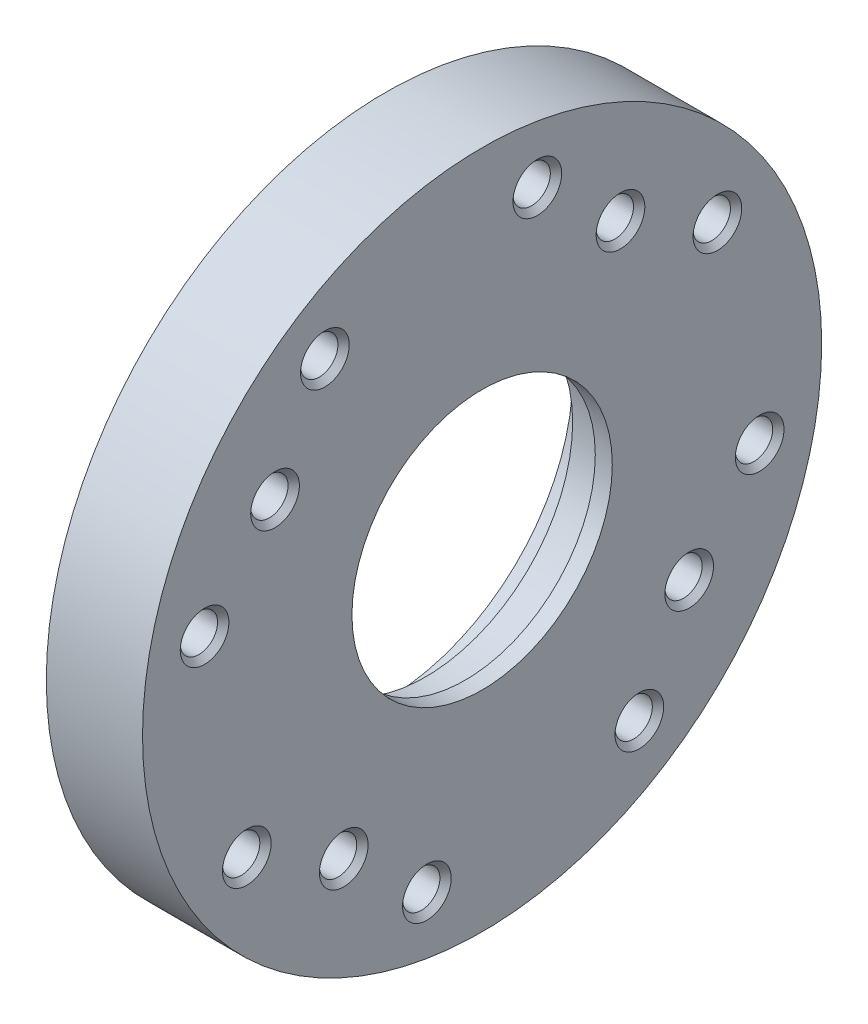
SolidWorks part; units mm, degrees
ref_plane "Front Plane" through (0, 0, 0) normal (0, 0, 1) x (1, 0, 0)
ref_plane "Top Plane" through (0, 0, 0) normal (0, 1, 0) x (1, 0, 0)
ref_plane "Right Plane" through (0, 0, 0) normal (1, 0, 0) x (0, 0, -1)
sketch "Sketch1" plane through (0, 0, 0) normal (0, 0, 1) x (1, 0, 0)
  line L0 (0, 0) -> (14, 0) construction
  line L1 (0, 60) -> (0, 33)
  line L2 (0, 33) -> (7, 33)
  line L3 (7, 33) -> (7, 26)
  line L4 (7, 26) -> (14, 26)
  line L5 (14, 26) -> (14, 23)
  line L6 (14, 23) -> (17, 23)
  line L7 (17, 23) -> (17, 60)
  line L8 (17, 60) -> (0, 60)
  dimension "D1" = 17
  dimension "D2" = 26
  dimension "D3" = 7
  dimension "D4" = 3
  dimension "D5" = 60
  dimension "D6" = 33
  dimension "D7" = 3
revolve "Revolve1" add sketch "Sketch1" angle 360 about L0
sketch "Sketch2" plane through (0, 0, 0) normal (-1, 0, 0) x (0, 0, 1)
  circle A0 centre (0, 0) radius 40 construction
  circle A1 centre (0, 40) radius 2.5
  circle A2 centre (15.3073, 36.9552) radius 2.5
  circle A3 centre (28.2843, 28.2843) radius 2.5
  circle A4 centre (36.9552, 15.3073) radius 2.5
  circle A5 centre (40, 0) radius 2.5
  circle A6 centre (36.9552, -15.3073) radius 2.5
  circle A7 centre (28.2843, -28.2843) radius 2.5
  circle A8 centre (15.3073, -36.9552) radius 2.5
  circle A9 centre (0, -40) radius 2.5
  circle A10 centre (-15.3073, -36.9552) radius 2.5
  circle A11 centre (-28.2843, -28.2843) radius 2.5
  circle A12 centre (-36.9552, -15.3073) radius 2.5
  circle A13 centre (-40, 0) radius 2.5
  circle A14 centre (-36.9552, 15.3073) radius 2.5
  circle A15 centre (-28.2843, 28.2843) radius 2.5
  circle A16 centre (-15.3073, 36.9552) radius 2.5
  point P37 (0, 0)
  dimension "D1" = 80
  dimension "D2" = 5
  dimension "D3" = 16
extrude "Cut-Extrude1" cut sketch "Sketch2" against normal blind 4
sketch "Sketch3" plane through (17, 0, 0) normal (1, 0, 0) x (0, 0, -1)
  circle A0 centre (49.0393, -9.7545) radius 3
  circle A1 centre (27.7785, -41.5735) radius 3
  circle A2 centre (-9.7545, -49.0393) radius 3
  circle A3 centre (-41.5735, -27.7785) radius 3
  circle A4 centre (-49.0393, 9.7545) radius 3
  circle A5 centre (-27.7785, 41.5735) radius 3
  circle A6 centre (9.7545, 49.0393) radius 3
  circle A7 centre (41.5735, 27.7785) radius 3
  point P20 (0, 0)
  dimension "D2" = 6
  dimension "D1" = 8
extrude "Cut-Extrude4" cut sketch "Sketch3" against normal through all
sketch "Sketch4" [suppressed] plane through (17, 0, 0) normal (1, 0, 0) x (0, 0, -1)
  circle A0 centre (9.7545, 49.0393) radius 5.25
  circle A1 centre (41.5735, 27.7785) radius 5.25
  circle A2 centre (49.0393, -9.7545) radius 5.25
  circle A3 centre (27.7785, -41.5735) radius 5.25
  circle A4 centre (-9.7545, -49.0393) radius 5.25
  circle A5 centre (-41.5735, -27.7785) radius 5.25
  circle A6 centre (-49.0393, 9.7545) radius 5.25
  circle A7 centre (-27.7785, 41.5735) radius 5.25
  point P20 (0, 0)
  dimension "D1" = 10.5
  dimension "D2" = 8
extrude "Cut-Extrude5" [suppressed] cut sketch "Sketch4" against normal blind 4
sketch "Sketch5" plane through (17, 0, 0) normal (1, 0, 0) x (0, 0, -1)
  line L0 (9.7545, 49.0393) -> (0, 0) construction
  line L1 (0, 0) -> (24.4451, 36.5847) construction
  circle A0 centre (9.7545, 49.0393) radius 3.3
  circle A1 centre (41.5735, 27.7785) radius 3.3
  circle A2 centre (49.0393, -9.7545) radius 3.3
  circle A3 centre (27.7785, -41.5735) radius 3.3
  circle A4 centre (-9.7545, -49.0393) radius 3.3
  circle A5 centre (-41.5735, -27.7785) radius 3.3
  circle A6 centre (-49.0393, 9.7545) radius 3.3
  circle A7 centre (-27.7785, 41.5735) radius 3.3
  circle A8 centre (0, 0) radius 44 construction
  circle A9 centre (24.4451, 36.5847) radius 3.3
  circle A10 centre (36.5847, -24.4451) radius 3.3
  circle A11 centre (-24.4451, -36.5847) radius 3.3
  circle A12 centre (-36.5847, 24.4451) radius 3.3
  point P19 (0, 0)
  point P33 (0, 0)
  dimension "D1" = 6.6
  dimension "D4" = 88
  dimension "D5" = 22.5
  dimension "D2" = 8
  dimension "D3" = 4
extrude "Cut-Extrude6" cut sketch "Sketch5" against normal blind 10
chamfer "Chamfer1" distance 1 angle 45 12 edges at (17, -27.7785, 38.2735) (17, -36.5847, 21.1451) (17, -49.0393, 6.4545) (17, -41.5735, -31.0785) (17, -24.4451, -39.8847) (17, -9.7545, -52.3393) (17, 27.7785, -44.8735) (17, 36.5847, -27.7451) (17, 49.0393, -13.0545) (17, 41.5735, 24.4785) (17, 24.4451, 33.2847) (17, 9.7545, 45.7393)
equation "\"R_ROLL\"= 5mm"
equation "\"D_SUN\"= 80mm"
equation "\"NUM_ROLL\"= 16"
equation "\"RHO\"= 1mm"
equation "\"D_SHAFT\"= 15mm"
equation "\"D_OUTPUT\"= 40mm"
equation "\"NUM_OUT\"= 6"
equation "\"R_OUT_ROLL\"= 5mm"
equation "\"D1@Sketch2\"=\"D_SUN\""
equation "\"D3@Sketch2\"=\"NUM_ROLL\""
